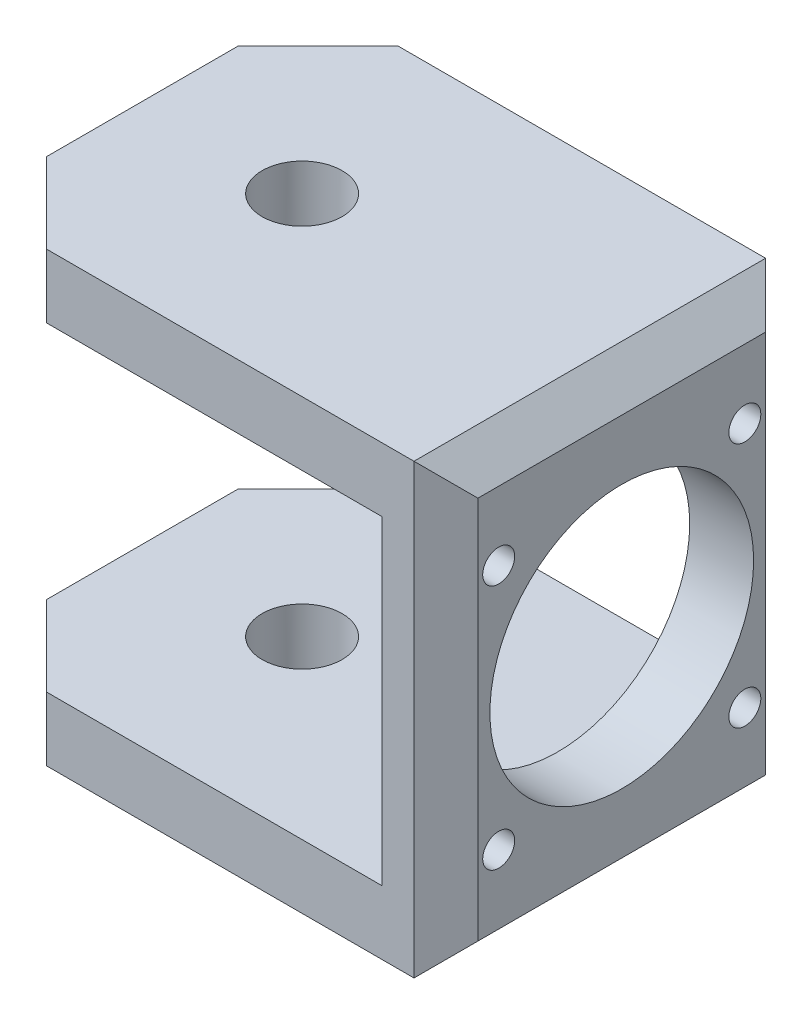
SolidWorks part; units mm, degrees
ref_plane "Front Plane" through (0, 0, 0) normal (0, 0, 1) x (1, 0, 0)
ref_plane "Top Plane" through (0, 0, 0) normal (0, 1, 0) x (1, 0, 0)
ref_plane "Right Plane" through (0, 0, 0) normal (1, 0, 0) x (0, 0, -1)
sketch "Sketch1" plane through (0, 0, 0) normal (0, 1, 0) x (1, 0, 0)
  line L1 (-15, -11) -> (15, -11)
  line L2 (-15, -11) -> (-15, 11)
  line L3 (-15, 11) -> (15, 11)
  line L4 (15, -11) -> (15, 11)
  line L5 (-15, -11) -> (15, 11) construction
  line L6 (-15, 11) -> (15, -11) construction
  point P0 (0, 0)
  dimension "D1" = 22
  dimension "D2" = 30
extrude "Boss-Extrude1" add sketch "Sketch1" along normal blind 4
sketch "Sketch2" plane through (0, 4, 0) normal (0, 1, 0) x (1, 0, 0)
  line L0 (-15, -11) -> (15, -11) construction
  line L1 (15, 11) -> (11, 11)
  line L2 (15, 11) -> (15, -11)
  line L3 (15, -11) -> (11, -11)
  line L4 (11, 11) -> (11, -11)
  dimension "D1" = 4
extrude "Boss-Extrude2" add sketch "Sketch2" along normal blind 20
sketch "Sketch3" plane through (0, 24, 0) normal (0, 1, 0) x (1, 0, 0)
  line L1 (15, 11) -> (-15, 11)
  line L2 (15, 11) -> (15, -11)
  line L3 (15, -11) -> (-15, -11)
  line L4 (-15, 11) -> (-15, -11)
extrude "Boss-Extrude3" add sketch "Sketch3" along normal blind 4
chamfer "Chamfer1" distance 5 angle 45 4 edges at (-15, 2, 11) (-15, 2, -11) (-15, 26, -11) (-15, 26, 11)
sketch "Sketch4" plane through (15, 0, 0) normal (1, 0, 0) x (0, 0, -1)
  circle A0 centre (0, 14) radius 8.25
  dimension "D1" = 16.5
extrude "Cut-Extrude1" cut sketch "Sketch4" against normal through all
ref_axis "Axis1" through (11, 14, 0) along (1, 0, 0)
sketch "Sketch5" plane through (15, 0, 0) normal (1, 0, 0) x (0, 0, -1)
  line L0 (0, 6.3) -> (-7.7, 6.3) construction
  line L1 (-7.7, 6.3) -> (0, 14) construction
  line L2 (0, 14) -> (0, 6.3) construction
  circle A0 centre (-7.7, 6.3) radius 1
  circle A1 centre (-7.7, 21.7) radius 1
  circle A2 centre (7.7, 21.7) radius 1
  circle A3 centre (7.7, 6.3) radius 1
  point P15 (0, 14)
  dimension "D3" = 2
  dimension "D1" = 45
  dimension "D2" = 7.7
  dimension "D4" = 4
extrude "Cut-Extrude2" cut sketch "Sketch5" against normal through all
chamfer "Chamfer2" distance 2 angle 45 4 edges at (15, 14, -11) (15, 0, 0) (15, 14, 11) (15, 28, 0)
sketch "Sketch6" plane through (0, 28, 0) normal (0, 1, 0) x (1, 0, 0)
  line L0 (11.1707, 0) -> (-17.3457, 0) construction
  line L1 (11, 0) -> (15, 0) construction
  line L2 (-15, 6) -> (-15, -6) construction
  circle A0 centre (-5, 0) radius 2.5
  dimension "D2" = 5
  dimension "D1" = 10
extrude "Cut-Extrude3" cut sketch "Sketch6" against normal through all
